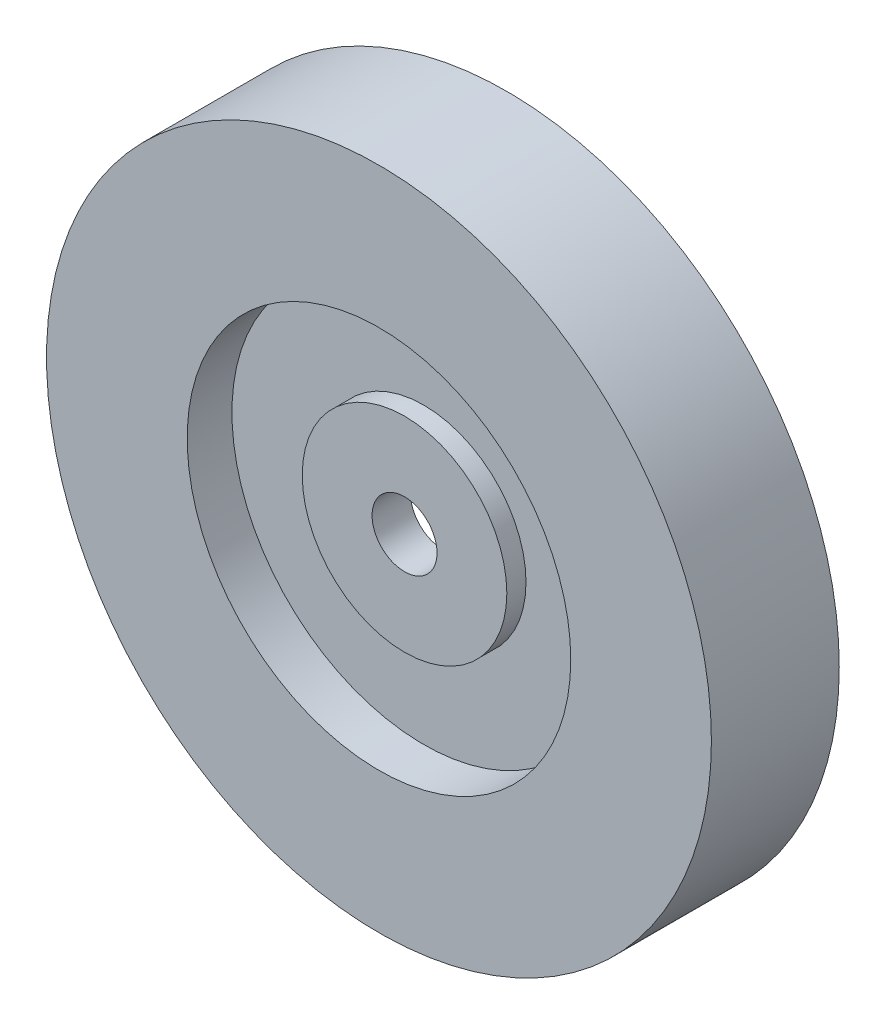
SolidWorks part; units mm, degrees
material "Caucho"
ref_plane "Front" through (0, 0, 0) normal (0, 0, 1) x (1, 0, 0)
ref_plane "Top" through (0, 0, 0) normal (0, 1, 0) x (1, 0, 0)
ref_plane "Right" through (0, 0, 0) normal (1, 0, 0) x (0, 0, -1)
sketch "Croquis1" plane through (0, 0, 0) normal (0, 0, 1) x (1, 0, 0)
  circle A0 centre (0, 0) radius 25.4
  circle A1 centre (0, 0) radius 80
  circle A2 centre (0, 0) radius 260
  circle A3 centre (0, 0) radius 150
  dimension "D1" = 50.8
  dimension "D2" = 160
  dimension "D3" = 520
  dimension "D4" = 300
extrude "Saliente-Extruir1" add sketch "Croquis1" along normal mid plane 100 contours A2 A3 region at (-252.6461, 0, 0)
extrude "Saliente-Extruir2" add sketch "Croquis1<3>" along normal mid plane 30 contours A3 A1 region at (-145.7574, 0, 0)
sketch "Croquis1<3>" plane through (0, 0, 0) normal (0, 0, 1) x (1, 0, 0) same geometry as "Croquis1"
extrude "Saliente-Extruir3" add sketch "Croquis1<4>" along normal blind 30 contours A1 A0 region at (-77.7373, 0, 0)
sketch "Croquis1<4>" plane through (0, 0, 0) normal (0, 0, 1) x (1, 0, 0) same geometry as "Croquis1"
